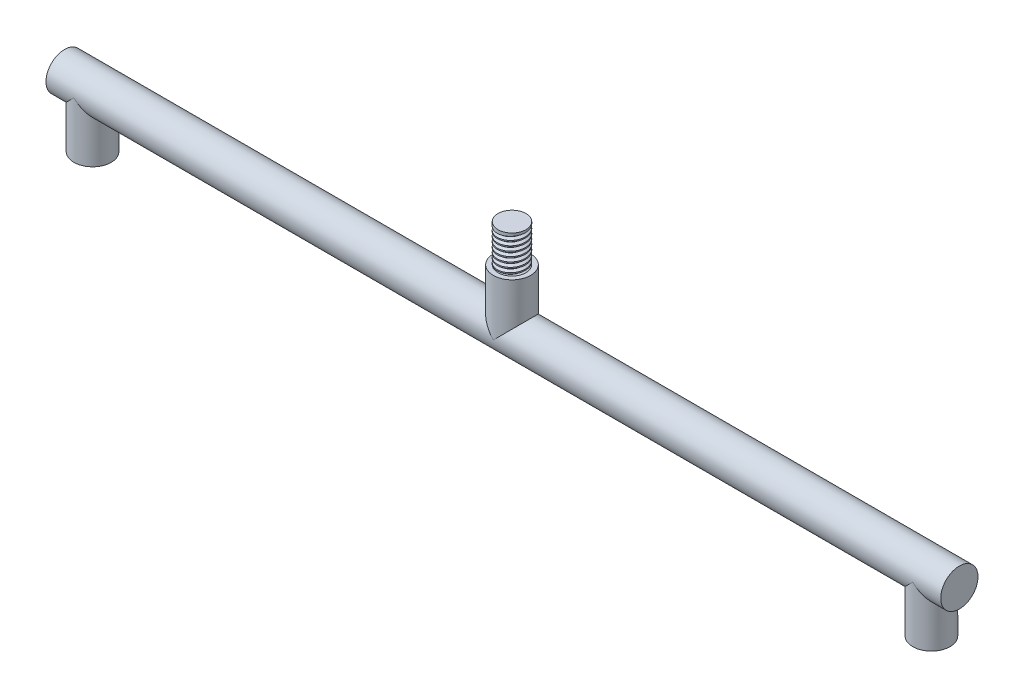
SolidWorks part; units mm, degrees
ref_plane "Front Plane" through (0, 0, 0) normal (0, 0, 1) x (1, 0, 0)
ref_plane "Top Plane" through (0, 0, 0) normal (0, 1, 0) x (1, 0, 0)
ref_plane "Right Plane" through (0, 0, 0) normal (1, 0, 0) x (0, 0, -1)
sketch "Sketch3" plane through (0, 0, 0) normal (0, 1, 0) x (1, 0, 0)
  line L0 (-23.1625, 0) -> (24.8375, 0) construction
  dimension "D1" = 48
sketch "Sketch5" plane through (0, 0, 0) normal (1, 0, 0) x (0, 0, -1)
  circle A0 centre (0, 0) radius 1
  dimension "D1" = 2
extrude "Boss-Extrude1" add sketch "Sketch5" along normal mid plane 48
sketch "Sketch6" plane through (0, 0, 0) normal (0, 1, 0) x (1, 0, 0)
  circle A0 centre (0, 0) radius 1
  dimension "D1" = 2
extrude "Boss-Extrude2" add sketch "Sketch6" along normal blind 5
sketch "Sketch7" plane through (0, 5, 0) normal (0, 1, 0) x (1, 0, 0)
  circle A0 centre (0, 0) radius 0.75
  dimension "D1" = 1.5
extrude "Cut-Extrude1" cut sketch "Sketch7" against normal blind 2 flip side to cut
thread "Thread1" pitch 0.25 method cut profile "Thread Profile1" start angle 0, offset 0, length 2, pitch 0.25, diameter 1.5
ref_plane "Plane1" through (-0.75, 5, 0) normal (0, 0, -1) x (1, 0, 0)
sketch "Thread Profile1" plane through (-0.75, 5, 0) normal (0, 0, -1) x (1, 0, 0)
  line L0 (0, 0) -> (0, 0.25) construction
  line L1 (0, 0) -> (0.1353, 0.0781)
  line L2 (0.1353, 0.0781) -> (0.1353, 0.1094)
  line L3 (0.1353, 0.1094) -> (0, 0.1875)
  line L4 (0.1353, 0.0937) -> (0, 0.0937) construction
  line L11 (0, 0) -> (0, 0.1875)
  point P2 (0, 0)
  dimension "Pitch" = 0.25
  dimension "Profile_Angle" = 60
  dimension "Profile_Land" = 0.0312
  dimension "Profile_Height" = 0.1353
sketch "Sketch10" plane through (0, 0, 0) normal (0, 0, -1) x (-1, 0, 0)
  line L4 (0.6147, 4.9219) -> (0.6147, 4.8906)
  line L5 (0.6147, 4.8906) -> (0.75, 4.8125)
  line L6 (0.75, 4.8125) -> (0.75, 5)
  line L7 (0.75, 5) -> (0.6147, 4.9219)
  line L8 (0.6147, 4.9219) -> (0.6147, 4.8906)
  line L9 (0.6147, 4.8906) -> (0.75, 4.8125)
  line L10 (0.75, 4.8125) -> (0.75, 5)
  line L11 (0.75, 5) -> (0.6147, 4.9219)
  dimension "D1" = 0
extrude "Cut-Extrude2" cut sketch "Sketch10" against normal blind 2
sketch "Sketch11" plane through (0, 0, 0) normal (0, 1, 0) x (1, 0, 0)
  line L0 (-24, 1) -> (-24, -1) construction
  line L1 (24, -1) -> (24, 1) construction
  circle A0 centre (-22.5, 0) radius 1
  circle A1 centre (22.5, 0) radius 1
  dimension "D1" = 2
  dimension "D2" = 2
  dimension "D3" = 1.5
  dimension "D4" = 1.5
extrude "Boss-Extrude3" add sketch "Sketch11" against normal blind 3
sketch "Sketch12" plane through (0, -3, 0) normal (0, -1, 0) x (1, 0, 0)
  circle A0 centre (-22.5, 0) radius 0.75
  circle A1 centre (22.5, 0) radius 0.75
  dimension "D1" = 1.5
  dimension "D2" = 1.5
extrude "Cut-Extrude3" cut sketch "Sketch12" against normal blind 1.5
thread "Thread2" pitch 0.25 method cut profile "Thread Profile2" start angle 0, offset 0, length 1.5, pitch 0.25, diameter 1.5
ref_plane "Plane2" through (-21.75, -3, 0) normal (0, 0, 1) x (1, 0, 0)
sketch "Thread Profile2" plane through (-21.75, -3, 0) normal (0, 0, 1) x (1, 0, 0)
  line L0 (0, 0) -> (0, 0.25) construction
  line L1 (0, 0) -> (0.1353, 0.0781)
  line L2 (0.1353, 0.0781) -> (0.1353, 0.1094)
  line L3 (0.1353, 0.1094) -> (0, 0.1875)
  line L4 (0.1353, 0.0937) -> (0, 0.0937) construction
  line L11 (0, 0) -> (0, 0.1875)
  point P2 (0, 0)
  dimension "Pitch" = 0.25
  dimension "Profile_Angle" = 60
  dimension "Profile_Land" = 0.0312
  dimension "Profile_Height" = 0.1353
thread "Thread3" pitch 0.25 method cut profile "Thread Profile3" start angle 0, offset 0, length 1.5, pitch 0.25, diameter 1.5
ref_plane "Plane3" through (23.25, -3, 0) normal (0, 0, 1) x (1, 0, 0)
sketch "Thread Profile3" plane through (23.25, -3, 0) normal (0, 0, 1) x (1, 0, 0)
  line L0 (0, 0) -> (0, 0.25) construction
  line L1 (0, 0) -> (0.1353, 0.0781)
  line L2 (0.1353, 0.0781) -> (0.1353, 0.1094)
  line L3 (0.1353, 0.1094) -> (0, 0.1875)
  line L4 (0.1353, 0.0937) -> (0, 0.0937) construction
  line L11 (0, 0) -> (0, 0.1875)
  point P2 (0, 0)
  dimension "Pitch" = 0.25
  dimension "Profile_Angle" = 60
  dimension "Profile_Land" = 0.0312
  dimension "Profile_Height" = 0.1353
